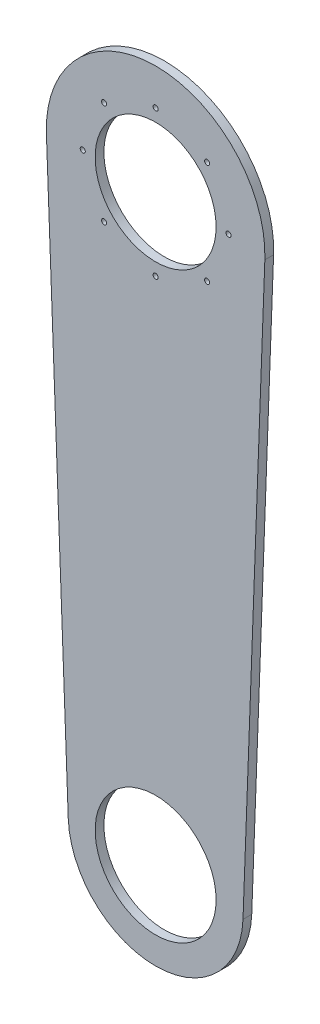
SolidWorks part; units mm, degrees
ref_plane "前视基准面" through (0, 0, 0) normal (0, 0, 1) x (1, 0, 0)
ref_plane "上视基准面" through (0, 0, 0) normal (0, 1, 0) x (1, 0, 0)
ref_plane "右视基准面" through (0, 0, 0) normal (1, 0, 0) x (0, 0, -1)
other "Configuration Table"
sketch "草图1" plane through (0, 0, 0) normal (0, 0, 1) x (1, 0, 0)
  line L0 (0, 435.7923) -> (0, -629.8791) construction
  line L1 (-74.9472, -2.8125) -> (-59.9578, -402.25)
  line L2 (74.9472, -2.8125) -> (59.9578, -402.25)
  arc A0 (74.9472, -2.8125) -> (-74.9472, -2.8125) centre (0, 0) ccw
  arc A1 (-59.9578, -402.25) -> (59.9578, -402.25) centre (0, -400) ccw
  circle A2 centre (0, 0) radius 41.5
  circle A3 centre (0, -400) radius 41.5
  dimension "D1" = 120
  dimension "D2" = 150
  dimension "D4" = 83
  dimension "D5" = 83
  dimension "D3" = 400
extrude "凸台-拉伸1" add sketch "草图1" along normal blind 6 contours L0 A3 | A3 L0 | A2 L0 | L0 A2 | L2 A1 L1 A0 region at (17.6131, 0, 0) region at (-17.6131, 0, 0) region at (17.6131, -400, 0) region at (-17.6131, -400, 0)
sketch "草图2" plane through (0, 0, 6) normal (0, 0, 1) x (1, 0, 0)
  line L0 (0, 0) -> (50, 0) construction
  circle A0 centre (50, 0) radius 1.75
  circle A1 centre (35.3553, -35.3553) radius 1.75
  circle A2 centre (0, -50) radius 1.75
  circle A3 centre (-35.3553, -35.3553) radius 1.75
  circle A4 centre (-50, 0) radius 1.75
  circle A5 centre (-35.3553, 35.3553) radius 1.75
  circle A6 centre (0, 50) radius 1.75
  circle A7 centre (35.3553, 35.3553) radius 1.75
  point P20 (0, 0)
  dimension "D1" = 3.5
  dimension "D2" = 50
  dimension "D3" = 8
extrude "切除-拉伸1" cut sketch "草图2" against normal blind 10
equation "\"、\"=6"
